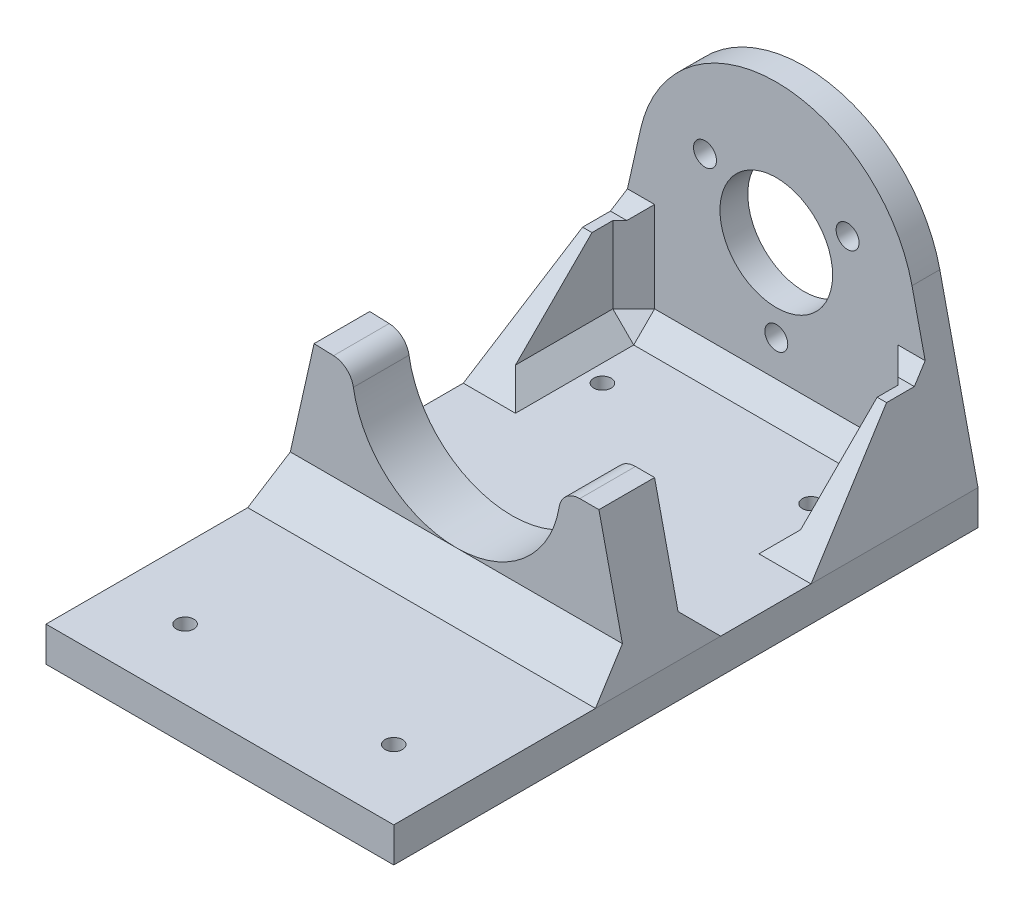
SolidWorks part; units mm, degrees
ref_plane "Plan de face" through (0, 0, 0) normal (0, 0, 1) x (1, 0, 0)
ref_plane "Plan de dessus" through (0, 0, 0) normal (0, 1, 0) x (1, 0, 0)
ref_plane "Plan de droite" through (0, 0, 0) normal (1, 0, 0) x (0, 0, -1)
sketch "Esquisse1" plane through (0, 0, 0) normal (0, 0, 1) x (1, 0, 0)
  line L0 (-25, -20) -> (-25, -25)
  line L1 (0, 0) -> (0, -30) construction
  line L2 (-25, -20) -> (-19.5122, 4.3902)
  line L3 (25, -20) -> (19.5122, 4.3902)
  line L4 (-25, -25) -> (25, -25)
  line L5 (25, -25) -> (25, -20)
  line L6 (0, -11.8357) -> (10.25, 5.9178) construction
  line L7 (10.25, 5.9178) -> (-10.25, 5.9178) construction
  line L8 (-10.25, 5.9178) -> (0, -11.8357) construction
  circle A0 centre (0, 0) radius 20 construction
  arc A1 (-19.5122, 4.3902) -> (19.5122, 4.3902) centre (0, 0) cw
  circle A2 centre (0, 0) radius 8.1
  circle A3 centre (0, 0) radius 5.9178 construction
  circle A4 centre (-10.25, 5.9178) radius 1.65
  circle A5 centre (10.25, 5.9178) radius 1.65
  circle A6 centre (0, -11.8357) radius 1.65
  point P20 (0, 0)
  point P24 (0, 0)
  dimension "D1" = 40
  dimension "D5" = 60
  dimension "D6" = 60
  dimension "D8" = 3.3
  dimension "D2" = 50
  dimension "D3" = 5
  dimension "D4" = 25
  dimension "D7" = 20.5
  dimension "D9" = 3
extrude "Boss.-Extru.1" add sketch "Esquisse1" along normal blind 4
sketch "Esquisse2" plane through (0, 0, 4) normal (0, 0, 1) x (1, 0, 0)
  line L0 (25, -25) -> (25, -20) construction
  line L1 (-25, -25) -> (25, -25)
  line L2 (-25, -25) -> (-25, -20)
  line L3 (-25, -20) -> (25, -20)
  line L4 (25, -25) -> (25, -20)
extrude "Boss.-Extru.2" add sketch "Esquisse2" along normal blind 80
sketch "Esquisse4" plane through (0, 0, 4) normal (0, 0, 1) x (1, 0, 0)
  line L0 (-20.5, 0) -> (-20.5, -20)
  line L1 (-19.5122, 4.3902) -> (-25, -20) construction
  line L2 (25, -20) -> (-25, -20) construction
  line L3 (-20.5, -20) -> (-25, -20)
  line L4 (-25, -20) -> (-25, -25) construction
  line L5 (-25, -20) -> (-20.5, 0)
  line L6 (0, 0) -> (0, -20) construction
  line L7 (25, -20) -> (-25, -20) construction
  line L8 (20.5, -20) -> (25, -20)
  line L9 (25, -20) -> (20.5, 0)
  line L10 (20.5, 0) -> (20.5, -20)
extrude "Boss.-Extru.3" add sketch "Esquisse4" along normal blind 20
sketch "Esquisse5" plane through (-20.5, 0, 0) normal (1, 0, 0) x (0, 0, -1)
  line L0 (-24, -20) -> (-4, 0) construction
  line L1 (-4, 0) -> (-24, 0)
  line L2 (-24, 0) -> (-24, -20)
  line L3 (-4, 0) -> (-4, -6)
  line L4 (-4, 0) -> (-4, 4.3902) construction
  line L5 (-4, -6) -> (-10, -6)
  line L6 (-10, -6) -> (-24, -20)
extrude "Enlèv. mat.-Extru.2" cut sketch "Esquisse5" against normal through all and the other way through all
chamfer "Chanfrein1" distance 3 angle 45 5 edges at (-20.5, -13, 4) (-20.5, -20, 14) (20.5, -13, 4) (20.5, -20, 14) (0, -20, 4)
chamfer "Chanfrein2" distance 2 angle 45 2 edges at (19.675, -6, 4) (-19.675, -6, 4)
ref_plane "Plan1" through (0, 0, 46) normal (0, 0, 1) x (1, 0, 0)
sketch "Esquisse7" plane through (0, 0, 46) normal (0, 0, 1) x (1, 0, 0)
  line L0 (-15, 0) -> (-20.4561, 0.1951)
  line L1 (-19.5122, 4.3902) -> (-21.4, -4) construction
  line L2 (-20.4561, 0.1951) -> (-25, -20)
  line L3 (-25, -20) -> (25, -20)
  line L4 (25, -20) -> (20.5, 0)
  line L5 (21.4, -4) -> (19.5122, 4.3902) construction
  line L6 (20.5, 0) -> (15, 0)
  arc A0 (-15, 0) -> (15, 0) centre (0, 0) ccw
  point P0 (0, 0)
extrude "Boss.-Extru.4" add sketch "Esquisse7" along normal blind 4 and the other way blind 4
chamfer "Chanfrein3" distance 5 angle 45 2 edges at (0, -20, 42) (0, -20, 50)
sketch "Esquisse6" plane through (0, -20, 0) normal (0, 1, 0) x (1, 0, 0)
  line L0 (0, 0) -> (0, -84) construction
  line L1 (25, -84) -> (-25, -84) construction
  line L2 (-25, -44) -> (25, -44) construction
  line L3 (-25, -84) -> (-25, -55) construction
  line L4 (25, -84) -> (25, -55) construction
  circle A0 centre (-15, -74) radius 1.25
  circle A1 centre (15, -74) radius 1.25
  circle A2 centre (15, -14) radius 1.25
  circle A3 centre (-15, -14) radius 1.25
  circle A4 centre (-15, -44) radius 1.25
  circle A5 centre (15, -44) radius 1.25
  dimension "D2" = 10
  dimension "D1" = 40
  dimension "D3" = 10
  dimension "D4" = 2
extrude "Enlèv. mat.-Extru.3" cut sketch "Esquisse6" against normal blind 20 and the other way blind 5
fillet "Congé1" radius 3 2 edges at (15, 0, 46) (-15, 0, 46)
